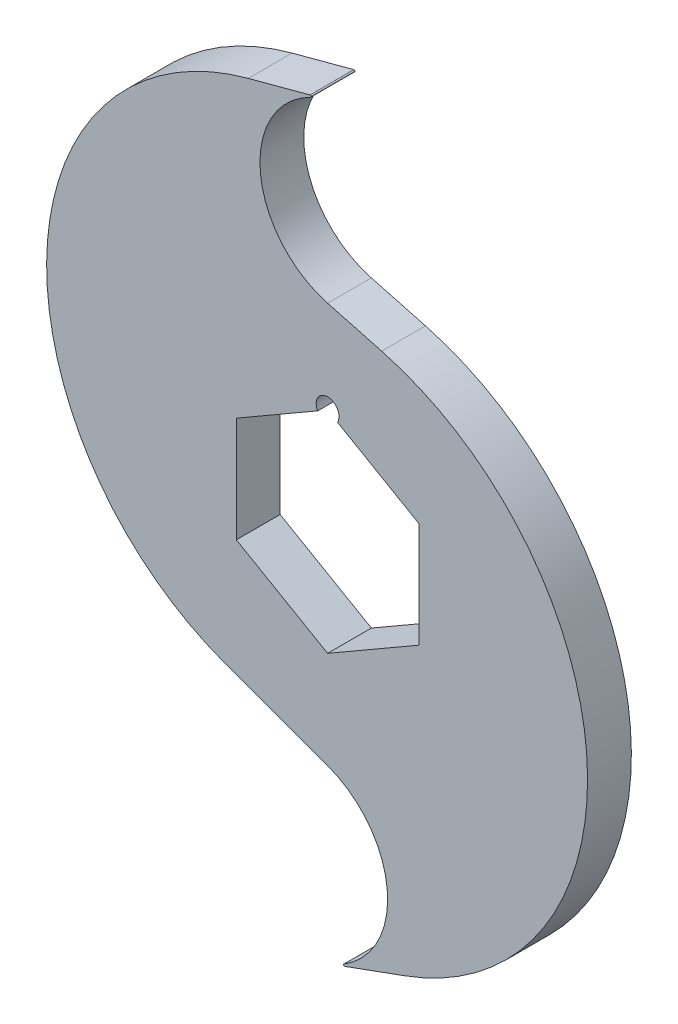
SolidWorks part; units mm, degrees
ref_plane "Front Plane" through (0, 0, 0) normal (0, 0, 1) x (1, 0, 0)
ref_plane "Top Plane" through (0, 0, 0) normal (0, 1, 0) x (1, 0, 0)
ref_plane "Right Plane" through (0, 0, 0) normal (1, 0, 0) x (0, 0, -1)
sketch "Sketch1" plane through (0, 0, 0) normal (0, 0, 1) x (1, 0, 0)
  line L0 (0, 52.07) -> (-11.0405, 49.1117)
  line L1 (0, 52.07) -> (0, 0) construction
  line L2 (0, -52.07) -> (10.7407, -48.1607)
  line L3 (0, 0) -> (0, -52.07) construction
  line L5 (0, 14.6647) -> (-12.7, 7.3323)
  line L6 (-12.7, 7.3323) -> (-12.7, -7.3323)
  line L7 (-12.7, -7.3323) -> (0, -14.6647)
  line L8 (0, -14.6647) -> (12.7, -7.3323)
  line L9 (12.7, -7.3323) -> (12.7, 7.3323)
  line L10 (12.7, 7.3323) -> (0, 14.6647)
  line L11 (0, 27.5355) -> (7.5237, 25.5195)
  line L12 (0, -28.2018) -> (-14.1906, -23.0368)
  circle A0 centre (0, 0) radius 52.07 construction
  arc A1 (0, 52.07) -> (0, 27.5355) centre (3.287, 39.8027) ccw
  arc A3 (0, -52.07) -> (0, -28.2018) centre (-4.3437, -40.1359) ccw
  arc A4 (10.7407, -48.1607) -> (7.5237, 25.5195) centre (-2.4834, -11.8278) ccw
  arc A5 (-11.0405, 49.1117) -> (-14.1906, -23.0368) centre (-1.2414, 12.5408) ccw
  circle A6 centre (0, 0) radius 12.7 construction
  circle A7 centre (0, 14.6647) radius 1.5875
  dimension "D4" = 70
  dimension "D5" = 25.4
  dimension "D1" = 104.14
  dimension "D6" = 12.7
  dimension "D7" = 3.175
  dimension "D2" = 11.43
  dimension "D3" = 75
extrude "Boss-Extrude1" add sketch "Sketch1" along normal mid plane 6.096 contours L0 A5 L12 A3 L2 A4 L11 A1 A7 L10 L9 L8 L7 L6 L5 region at (-10.698, 39.8027, 0)
fillet "Fillet1" radius 0.127 2 edges at (0, 52.07, 0) (0, -52.07, 0)
